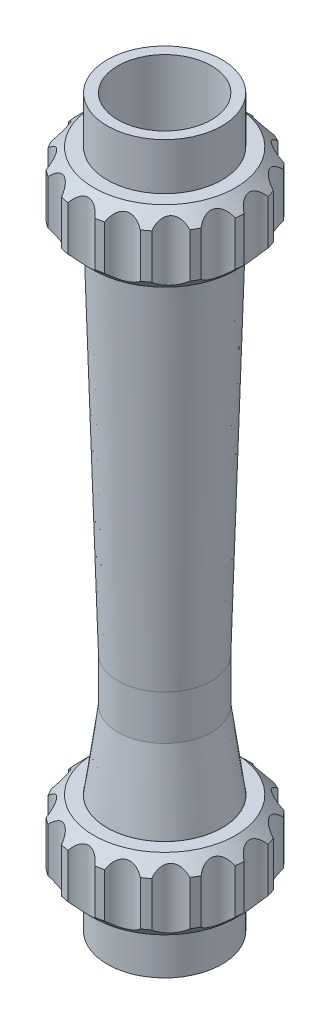
SolidWorks part; units mm, degrees
ref_plane "Front Plane" through (0, 0, 0) normal (0, 0, 1) x (1, 0, 0)
ref_plane "Top Plane" through (0, 0, 0) normal (0, 1, 0) x (1, 0, 0)
ref_plane "Right Plane" through (0, 0, 0) normal (1, 0, 0) x (0, 0, -1)
sketch "Rotameter" plane through (0, 0, 0) normal (0, 0, 1) x (1, 0, 0)
  line L0 (-20, 310) -> (-24.5, 310)
  line L1 (-20, 0) -> (-20, 30.5)
  line L2 (-24.5, 310) -> (-24.5, 290)
  line L3 (-20, 30.5) -> (0, 30.5)
  line L4 (-24.5, 290) -> (-30.25, 290)
  line L5 (-30.25, 290) -> (-36, 284.25)
  line L6 (-36, 284.25) -> (-36, 265.25)
  line L7 (-36, 265.25) -> (-30.25, 259.5)
  line L8 (-30.25, 259.5) -> (-24.6, 259.5)
  line L10 (-24.5, 259.5) -> (-20, 102.5282)
  line L11 (-20, 102.5282) -> (-20, 83.5282)
  line L12 (-20, 83.5282) -> (-24.5, 50.5)
  line L13 (-36, 155) -> (36, 155) construction
  line L14 (-30.25, 50.5) -> (-24.6, 50.5)
  line L15 (-36, 44.75) -> (-30.25, 50.5)
  line L16 (-36, 25.75) -> (-36, 44.75)
  line L17 (-30.25, 20) -> (-36, 25.75)
  line L18 (-24.5, 20) -> (-30.25, 20)
  line L19 (-24.5, 0) -> (-24.5, 20)
  line L20 (-20, 0) -> (-24.5, 0)
  line L21 (-20, 279.5) -> (0, 279.5)
  line L22 (0, 30.5) -> (0, 36.15)
  line L23 (0, 0) -> (0, -4.5) construction
  line L24 (-20, 310) -> (-20, 279.5)
  line L25 (-30.25, 50.5) -> (-30.25, 20) construction
  line L26 (-36, 35.25) -> (-30.25, 35.25) construction
  line L27 (-30.25, 35.25) -> (-24.5, 35.25) construction
  line L28 (-24.5, 36.25) -> (-24.5, 50.5)
  line L29 (-24.6, 50.5) -> (-24.6, 36.15)
  line L30 (-24.6, 36.15) -> (0, 36.15)
  line L31 (-24.5, 36.25) -> (0, 36.25)
  line L32 (0, 36.25) -> (0, 273.75)
  line L33 (-24.6, 273.85) -> (0, 273.85)
  line L34 (-24.5, 273.75) -> (0, 273.75)
  line L35 (-24.5, 273.75) -> (-24.5, 259.5)
  line L36 (-24.6, 259.5) -> (-24.6, 273.85)
  line L37 (0, 273.85) -> (0, 279.5)
  line L38 (-12.3, 36.15) -> (-12.3, 36.25) construction
  line L39 (-24.5, 43.375) -> (-24.6, 43.375) construction
  point P46 (0, 155)
  dimension "D5" = 72
  dimension "D6" = 33.3333
  dimension "D7" = 0.1
revolve "Revolve1" add sketch "Rotameter" angle 360 about L23
sketch "Sketch4" plane through (0, 0, 0) normal (0, -1, 0) x (1, 0, 0)
  circle A0 centre (0, 39.7738) radius 7.1429
  circle A3 centre (0, 0) radius 30.25 construction
  dimension "D1" = 14.2857
  dimension "D2" = 2.381
extrude "Cut-Extrude1" cut sketch "Sketch4" against normal through all
pattern_circular "CirPattern1" count 15 over 360 about axis through (0, 0, 0) along (0, 1, 0) of "Cut-Extrude1" reverse direction yes
other "CPoint1" parameters "Diameter"=25.4, "StubLength"=57.15
ref_axis "Axis1" through (0, 289.5, 0) along (0, -1, 0)
other "CPoint2" parameters "Diameter"=25.4, "StubLength"=57.15
ref_axis "Axis2" through (0, 20.5, 0) along (0, 1, 0)
other "RPoint1" [suppressed]
ref_axis "Vertical" [suppressed] through (-28.8, 127.5, 0) along (1, 0, 0)
equation "\"D5@Rotameter\"=\"B1@Rotameter\" * 1.8"
equation "\"D6@Rotameter\" = \"B1@Rotameter\" / 1.2"
equation "\"D1@Sketch4\"=\"B1@Rotameter\"/2.8"
equation "\"D2@Sketch4\"=\"D1@Sketch4\"/6"
